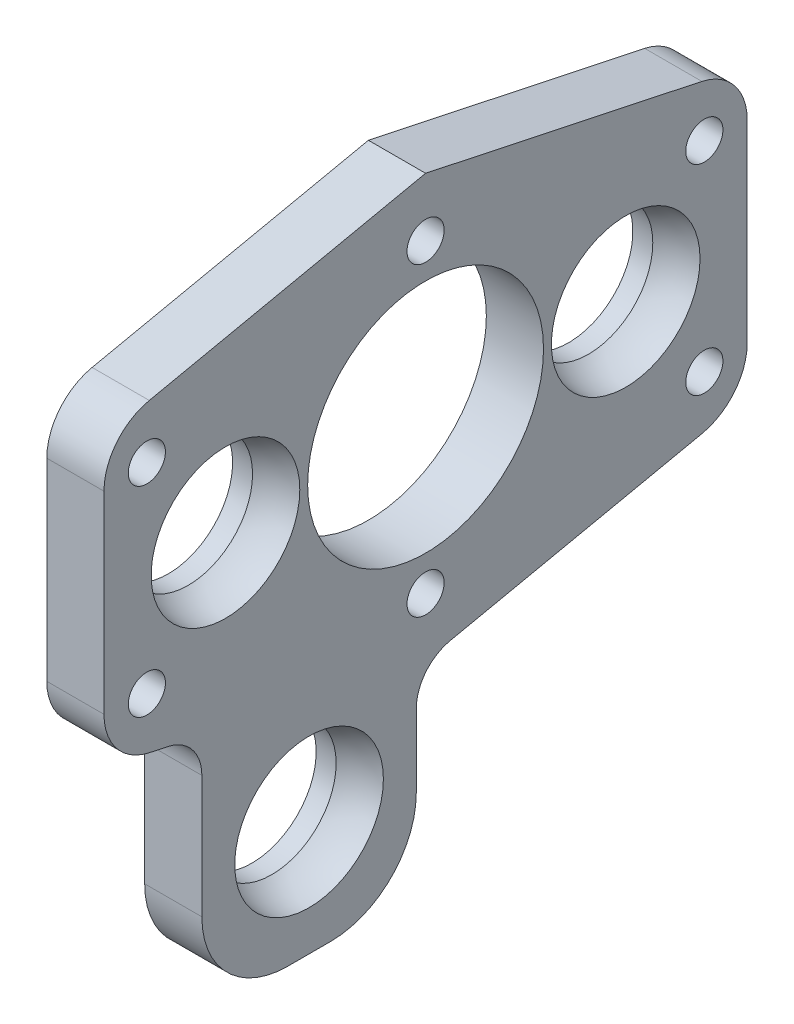
SolidWorks part; units mm, degrees
ref_plane "Front" through (0, 0, 0) normal (0, 0, 1) x (1, 0, 0)
ref_plane "Top" through (0, 0, 0) normal (0, 1, 0) x (1, 0, 0)
ref_plane "Right" through (0, 0, 0) normal (1, 0, 0) x (0, 0, -1)
sketch "Sketch1" plane through (0, 0, 0) normal (1, 0, 0) x (0, 0, -1)
  line L0 (0, 0) -> (22.5, 4.7697)
  line L1 (0, 0) -> (45, 0)
  line L2 (0, 0) -> (0, -20)
  line L3 (0, -20) -> (45, -20)
  line L4 (45, 0) -> (45, -20)
  line L5 (22.5, 4.7697) -> (45, 0)
  line L6 (0, -20) -> (22.5, -24.7697)
  line L7 (22.5, -24.7697) -> (45, -20)
  circle A0 centre (22.5, 0.6808) radius 1.3
  circle A1 centre (22.5, -20.6808) radius 1.3
  circle A2 centre (3, -3) radius 1.3
  circle A3 centre (42, -3) radius 1.3
  circle A4 centre (42, -17) radius 1.3
  circle A5 centre (3, -17) radius 1.3
  dimension "D7" = 2.6
  dimension "D8" = 2.6
  dimension "D13" = 2.6
  dimension "D1" = 45
  dimension "D2" = 20
  dimension "D3" = 23
  dimension "D4" = 23
  dimension "D5" = 23
  dimension "D6" = 23
  dimension "D9" = 4
  dimension "D10" = 4
  dimension "D11" = 4
  dimension "D12" = 4
  dimension "D14" = 3
  dimension "D15" = 3
  dimension "D16" = 2
  dimension "D17" = 2
extrude "Boss-Extrude1" add sketch "Sketch1" along normal blind 4 contours L4 L1 L2 L3 | L5 L0 L1 A0 | L6 L7 L3 A1 region at (0, 1.9422, -11.3438) region at (0, -10, -22.5) region at (0, -20.4525, -10.6963)
sketch "Sketch2" plane through (4, 0, 0) normal (1, 0, 0) x (0, 0, -1)
  line L0 (0, 0) -> (0, -20) construction
  line L1 (3.3, -10) -> (13.7, -10)
  line L2 (31.3, -10) -> (41.7, -10)
  arc A0 (13.7, -10) -> (3.3, -10) centre (8.5, -10) ccw
  arc A1 (41.7, -10) -> (31.3, -10) centre (36.5, -10) ccw
  dimension "D1" = 10.4
  dimension "D2" = 8.5
  dimension "D3" = 10
  dimension "D4" = 2
revolve "Cut-Revolve1" cut sketch "Sketch2" angle 360 about L1
sketch "Sketch3" plane through (4, 0, 0) normal (1, 0, 0) x (0, 0, -1)
  line L0 (0, 0) -> (0, -20) construction
  circle A0 centre (22.5, -10) radius 8.25
  dimension "D1" = 16.5
  dimension "D2" = 22.5
  dimension "D3" = 10
extrude "Cut-Extrude1" cut sketch "Sketch3" against normal through all
sketch "Sketch4" plane through (0, 0, 0) normal (-1, 0, 0) x (0, 0, 1)
  circle A0 centre (-8.5, -10) radius 4.5
  circle A1 centre (-36.5, -10) radius 4.5
  circle A2 centre (-36.5, -10) radius 3.3226 construction
  circle A3 centre (-8.5, -10) radius 3.3226 construction
  dimension "D1" = 9
  dimension "D2" = 9
  dimension "D3" = 0
  dimension "D4" = 0
extrude "Cut-Extrude2" cut sketch "Sketch4" against normal through all
sketch "Sketch5" plane through (4, 0, 0) normal (1, 0, 0) x (0, 0, -1)
  line L0 (6.8478, -21.4516) -> (21.8478, -24.6314)
  line L1 (0, -20) -> (22.5, -24.7697) construction
  line L2 (21.8478, -24.6314) -> (21.8478, -38.4516)
  line L3 (21.8478, -38.4516) -> (6.8478, -38.4516)
  line L4 (6.8478, -38.4516) -> (6.8478, -21.4516)
  dimension "D1" = 15
  dimension "D2" = 17
  dimension "D3" = 7
extrude "Boss-Extrude2" add sketch "Sketch5" against normal blind 4
sketch "Sketch6" plane through (4, 0, 0) normal (1, 0, 0) x (0, 0, -1)
  line L0 (6.8478, -21.4516) -> (6.8478, -38.4516) construction
  line L1 (6.8478, -38.4516) -> (21.8478, -38.4516) construction
  line L2 (14.3478, -25.2516) -> (14.3478, -35.6516)
  arc A0 (14.3478, -25.2516) -> (14.3478, -35.6516) centre (14.3478, -30.4516) ccw
  dimension "D1" = 10.4
  dimension "D2" = 7.5
  dimension "D3" = 8
revolve "Cut-Revolve2" cut sketch "Sketch6" angle 360 about L2
sketch "Sketch7" plane through (0, 0, 0) normal (-1, 0, 0) x (0, 0, 1)
  circle A0 centre (-14.3478, -30.4516) radius 4.5
  circle A1 centre (-14.3478, -30.4516) radius 3.3226 construction
  dimension "D1" = 9
  dimension "D2" = 0
extrude "Cut-Extrude3" cut sketch "Sketch7" against normal through all
fillet "Fillet1" radius 6 2 edges at (2, -38.4516, -21.8478) (2, -38.4516, -6.8478)
fillet "Fillet2" radius 4 4 edges at (2, 0, 0) (2, -20, 0) (2, -20, -45) (2, 0, -45)
fillet "Fillet3" radius 3 2 edges at (2, -24.6314, -21.8478) (2, -21.4516, -6.8478)
fillet "Fillet4" radius 3 1 edges at (2, -24.7697, -22.5)
